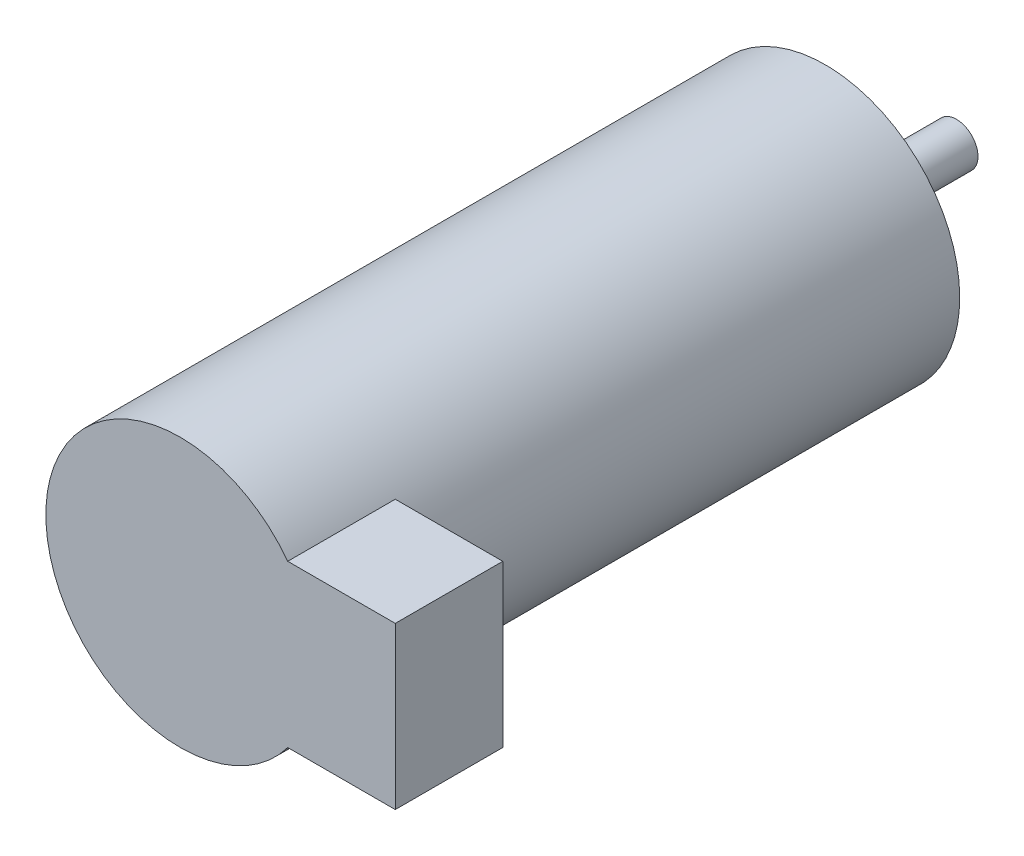
SolidWorks part; units mm, degrees
material "1060 Alloy"
ref_plane "Front Plane" through (0, 0, 0) normal (0, 0, 1) x (1, 0, 0)
ref_plane "Top Plane" through (0, 0, 0) normal (0, 1, 0) x (1, 0, 0)
ref_plane "Right Plane" through (0, 0, 0) normal (1, 0, 0) x (0, 0, -1)
sketch "Sketch1" plane through (0, 0, 0) normal (0, 0, 1) x (1, 0, 0)
  circle A0 centre (0, 0) radius 12.5
  dimension "D1" = 25
extrude "Boss-Extrude1" add sketch "Sketch1" along normal blind 60
sketch "Sketch2" plane through (0, 0, 0) normal (0, 0, 1) x (1, 0, 0)
  line L0 (-8.5, 0) -> (0, 0) construction
  line L1 (0, 0) -> (8.5, 0) construction
  circle A0 centre (0, 0) radius 3.5
  circle A1 centre (0, 0) radius 2
  circle A2 centre (8.5, 0) radius 1.5
  circle A3 centre (-8.5, 0) radius 1.5
  circle A4 centre (0, 0) radius 12.5 construction
  point P8 (-10, 0)
  point P9 (-12.5, 0)
  dimension "D1" = 3
  dimension "D2" = 4
  dimension "D3" = 7
  dimension "D4" = 17
extrude "Cut-Extrude1" cut sketch "Sketch2" along normal blind 3.5 contours A2 | A3
extrude "Boss-Extrude2" add sketch "Sketch2<3>" against normal blind 2.5 contours A0 A1 region at (-3.401, 0, 0)
sketch "Sketch2<3>" plane through (0, 0, 0) normal (0, 0, 1) x (1, 0, 0) same geometry as "Sketch2"
extrude "Boss-Extrude3" add sketch "Sketch2<4>" against normal blind 12.2 contours A1
sketch "Sketch2<4>" plane through (0, 0, 0) normal (0, 0, 1) x (1, 0, 0) same geometry as "Sketch2"
sketch "Sketch3" plane through (0, 0, 0) normal (1, 0, 0) x (0, 0, -1)
  line L0 (-60, 12.5) -> (-60, -12.5) construction
  line L1 (-60, 7.5) -> (-50, 7.5)
  line L2 (-60, 7.5) -> (-60, -7.5)
  line L3 (-60, -7.5) -> (-50, -7.5)
  line L4 (-50, 7.5) -> (-50, -7.5)
  point P5 (-50, 0)
  dimension "D1" = 15
  dimension "D2" = 10
extrude "Boss-Extrude4" add sketch "Sketch3" along normal blind 20
